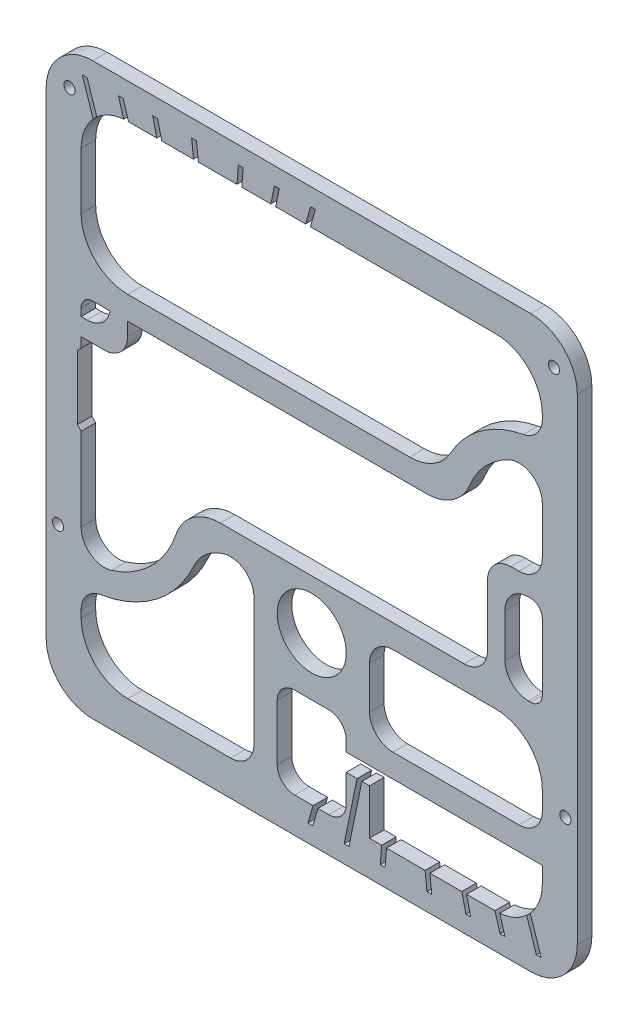
SolidWorks part; units mm, degrees
ref_plane "Front Plane" through (0, 0, 0) normal (0, 0, 1) x (1, 0, 0)
ref_plane "Top Plane" through (0, 0, 0) normal (0, 1, 0) x (1, 0, 0)
ref_plane "Right Plane" through (0, 0, 0) normal (1, 0, 0) x (0, 0, -1)
sketch "Sketch1" plane through (0, 0, 0) normal (0, 0, 1) x (1, 0, 0)
  line L0 (44.642, 23.7892) -> (44.642, 19.9792) construction
  line L1 (-8.1388, 23.7892) -> (49.7286, 23.7892)
  line L2 (-8.1388, 23.7892) -> (-8.1388, -38.311)
  line L3 (-8.1388, -38.311) -> (49.7286, -38.311)
  line L4 (49.7286, 23.7892) -> (49.7286, -38.311)
  line L5 (45.9186, -34.501) -> (-4.3288, -34.501)
  line L6 (45.9186, -34.501) -> (45.9186, 19.9792)
  line L7 (45.9186, 19.9792) -> (-4.3288, 19.9792)
  line L8 (-4.3288, -34.501) -> (-4.3288, 19.9792)
  line L9 (44.642, 21.8842) -> (-35.1587, 21.8842) construction
  line L10 (-4.3288, -31.0517) -> (-8.1388, -31.0517) construction
  line L11 (-6.2338, -31.0517) -> (-6.2338, 6.9585) construction
  line L12 (20.6696, 21.8842) -> (21.1982, 21.8842) construction
  line L13 (-6.2338, -12.887) -> (-6.2338, -25.1298) construction
  line L14 (3.0779, -34.501) -> (3.0779, -38.311) construction
  line L15 (3.0779, -36.406) -> (37.3423, -36.406) construction
  line L17 (49.7286, 15.2205) -> (45.9186, 15.2205) construction
  line L18 (47.8236, 15.2205) -> (47.8236, -0.9437) construction
  line L19 (47.8236, -1.6348) -> (47.8236, 10.608) construction
  line L20 (20.9203, -36.406) -> (20.3916, -36.406) construction
  dimension "D1" = 3.81
  dimension "D2" = 3.81
extrude "Boss-Extrude1" add sketch "Sketch1" along normal blind 1.5875
sketch "Sketch2" plane through (0, 0, 0) normal (0, 0, -1) x (-1, 0, 0)
  line L0 (-45.9186, -34.501) -> (-45.9186, 19.9792) construction
  line L1 (-34.8696, 3.653) -> (4.3288, 3.653)
  line L2 (-45.9186, 3.653) -> (-45.9186, 0.7339)
  line L3 (-37.4096, 1.113) -> (4.3288, 1.113)
  line L4 (4.3288, 3.653) -> (4.3288, 1.113)
  line L5 (4.3288, 19.9792) -> (4.3288, -34.501) construction
  line L6 (-33.4496, 1.113) -> (-36.4496, 1.113) construction
  line L7 (1.2504, -12.887) -> (-36.4496, -12.887) construction
  line L8 (-45.9186, -15.427) -> (-8.8785, -15.427)
  line L9 (-45.9186, -15.427) -> (-45.9186, -12.887)
  line L10 (-45.9186, -12.887) -> (-6.5805, -12.887)
  line L11 (1.357, -21.2563) -> (14.2432, -21.2563) construction
  line L12 (4.3288, -23.7963) -> (4.3288, -26.3363)
  line L13 (-45.9186, 12.162) -> (-45.9186, 9.622)
  arc A0 (-45.9186, 9.622) -> (-37.4096, 1.113) centre (-45.9186, 1.113) cw
  arc A1 (-45.9186, 12.162) -> (-34.8696, 3.653) centre (-45.9186, 0.7339) cw
  arc A2 (4.3288, -23.7963) -> (-6.5805, -12.887) centre (4.3288, -12.887) cw
  arc A3 (-8.8785, -15.427) -> (4.3288, -26.3363) centre (4.3288, -12.887) ccw
  circle A5 centre (1.357, -18.2591) radius 2.9972 construction
  line M5 (-45.9186, -34.501) -> (-45.9186, 19.9792)
  line M7 (4.3288, 19.9792) -> (4.3288, -34.501)
  dimension "D5" = 2.54
  dimension "D1" = 2.54
  dimension "D2" = 2.54
  dimension "D3" = 2.54
  dimension "D4" = 2.54
  dimension "D6" = 2.54
  dimension "D7" = 2.54
extrude "Boss-Extrude2" add sketch "Sketch2" against normal up to surface (1.5875 mm away) contours A1 A0 L3 L1 M5 M7 | L10 L8 M5 M7 region at (15.2704, 3.1385, 0) region at (-3.8086, -25.0663, 0) up to face at (20.7949, -7.2609, 1.5875)
sketch "Sketch3" plane through (0, 0, 0) normal (0, 0, -1) x (-1, 0, 0)
  line L0 (-45.9186, -1.1649) -> (-39.9496, -1.1649)
  line L1 (-45.9186, -12.887) -> (-45.9186, 9.622) construction
  line L2 (-39.9496, -4.387) -> (-39.9496, -11.387) construction
  line L3 (-39.9496, -1.1649) -> (-39.9496, -12.887)
  line L4 (-45.9186, -12.887) -> (-6.5805, -12.887) construction
  line L5 (-39.9496, -12.887) -> (-41.8546, -12.887)
  line L6 (-41.8546, -12.887) -> (-41.8546, -3.0699)
  line L7 (-41.8546, -3.0699) -> (-45.9186, -3.0699)
  line L8 (-45.9186, -3.0699) -> (-45.9186, -1.1649)
  line L9 (-42.9468, 0.7401) -> (-53.4831, 0.7401) construction
  line L10 (-0.7296, 1.113) -> (-0.7296, -2.887)
  line L11 (-37.4096, 1.113) -> (4.3288, 1.113) construction
  line L12 (-1.9996, -2.887) -> (1.2504, -2.887) construction
  line L13 (-0.7296, -2.887) -> (4.3288, -2.887)
  line L14 (4.3288, 1.113) -> (4.3288, -23.7963) construction
  line L15 (4.3288, -2.887) -> (4.3288, -0.982)
  line L16 (4.3288, -0.982) -> (1.1754, -0.982)
  line L17 (1.1754, -0.982) -> (1.1754, 1.113)
  line L18 (1.1754, 1.113) -> (-0.7296, 1.113)
  circle A0 centre (-42.9468, 3.7373) radius 2.9972 construction
  dimension "D1" = 1.905
  dimension "D2" = 1.905
  dimension "D3" = 1.905
  dimension "D4" = 1.905
  dimension "D5" = 1.27
  dimension "D6" = 1.905
extrude "Boss-Extrude3" add sketch "Sketch3" against normal up to surface (1.5875 mm away) up to face at (21.2778, -6.3699, 1.5875)
fillet "Fillet1" radius 5.08 4 edges at (49.7286, -38.311, 0.7937) (-8.1388, -38.311, 0.7937) (-8.1388, 23.7892, 0.7937) (49.7286, 23.7892, 0.7937)
fillet "Fillet2" radius 5.08 10 edges at (8.8785, -15.427, 0.7937) (45.9186, -15.427, 0.7937) (45.9186, -34.501, 0.7937) (-4.3288, -34.501, 0.7937) (34.8696, 3.653, 0.7937) (-4.3288, 3.653, 0.7937) (45.9186, 19.9792, 0.7937) (-4.3288, 19.9792, 0.7937) (6.5805, -12.887, 0.7937) (37.4096, 1.113, 0.7937)
fillet "Fillet3" radius 2.54 11 edges at (41.8546, -3.0699, 0.7938) (39.9496, -12.887, 0.7938) (41.8546, -12.887, 0.7938) (39.9496, -1.1649, 0.7938) (45.9186, -1.1649, 0.7938) (-1.1754, -0.982, 0.7938) (0.7296, -2.887, 0.7938) (45.9186, 9.622, 0.7937) (-4.3288, -26.3363, 0.7937) (-4.3288, -23.7963, 0.7937) (45.9186, 12.162, 0.7937)
fillet "Fillet4" radius 1.27 3 edges at (45.9186, -12.887, 0.7937) (45.9186, -3.0699, 0.7938) (-4.3288, 1.113, 0.7937)
sketch "Sketch5" plane through (0, 0, 0) normal (0, 0, -1) x (-1, 0, 0)
  line L0 (-40.8386, -15.427) -> (-12.5612, -15.427) construction
  line L1 (-27.0941, -15.427) -> (-14.4957, -15.427)
  line L2 (-27.0941, -15.427) -> (-27.0941, -34.501)
  line L3 (-27.0941, -34.501) -> (-14.4957, -34.501)
  line L4 (-14.4957, -15.427) -> (-14.4957, -34.501)
  line L5 (-0.7512, -34.501) -> (-40.8386, -34.501) construction
  line L6 (-24.5541, -18.2972) -> (-27.0941, -18.2972) construction
  line L9 (-17.0357, -18.2972) -> (-14.4957, -18.2972) construction
  circle A1 centre (-20.7949, -18.2972) radius 3.7592 construction
  dimension "D1" = 2.54
extrude "Boss-Extrude4" add sketch "Sketch5" against normal up to surface (1.5875 mm away) up to face at (-3.29, -0.0173, 1.5875)
sketch "Sketch6" plane through (0, 0, 0) normal (0, 0, -1) x (-1, 0, 0)
  circle A0 centre (-20.7949, -18.2972) radius 3.7592 construction
  circle A1 centre (-20.7949, -18.2972) radius 3.7592
extrude "Cut-Extrude2" cut sketch "Sketch6" against normal up to surface (1.5875 mm away) up to face at (4.8008, -25.4732, 1.5875)
sketch "Sketch7" plane through (0, 0, 0) normal (0, 0, -1) x (-1, 0, 0)
  line L0 (-27.0941, -15.427) -> (-27.0941, -34.501) construction
  line L1 (-24.5541, -24.5964) -> (-17.0357, -24.5964)
  line L2 (-24.5541, -24.5964) -> (-24.5541, -34.501)
  line L3 (-24.5541, -34.501) -> (-17.0357, -34.501)
  line L4 (-17.0357, -24.5964) -> (-17.0357, -34.501)
  line L5 (-14.4957, -34.501) -> (-14.4957, -15.427) construction
  line L6 (-0.7512, -34.501) -> (-14.4957, -34.501) construction
  line L7 (-20.7949, -22.0564) -> (-6.5424, -22.0564) construction
  line L8 (-20.7949, -22.0564) -> (-20.7949, -21.3452) construction
  circle A0 centre (-20.7949, -18.2972) radius 3.7592 construction
  dimension "D1" = 2.54
  dimension "D2" = 2.54
  dimension "D3" = 2.54
extrude "Cut-Extrude3" cut sketch "Sketch7" against normal up to surface (1.5875 mm away) up to face at (24.5541, -18.2972, 1.5875)
fillet "Fillet5" radius 1.905 4 edges at (24.5541, -34.501, 0.7937) (17.0357, -34.501, 0.7938) (17.0357, -24.5964, 0.7938) (24.5541, -24.5964, 0.7938)
sketch "Sketch8" plane through (0, 0, 0) normal (0, 0, -1) x (-1, 0, 0)
  line L0 (-45.9186, -29.421) -> (-45.9186, -20.507) construction
  line L1 (-45.9186, -25.103) -> (-27.0941, -25.103)
  line L2 (-45.9186, -25.103) -> (-45.9186, -27.643)
  line L3 (-45.9186, -27.643) -> (-27.0941, -27.643)
  line L4 (-27.0941, -25.103) -> (-27.0941, -27.643)
  line L5 (-27.0941, -15.427) -> (-27.0941, -34.501) construction
  line L6 (-45.7916, -27.643) -> (-20.3916, -27.643) construction
  dimension "D1" = 2.54
extrude "Boss-Extrude5" add sketch "Sketch8" against normal up to surface (1.5875 mm away) up to face at (20.7949, -29.5487, 1.5875)
fillet "Fillet6" radius 2.54 5 edges at (27.0941, -15.427, 0.7937) (14.4957, -15.427, 0.7937) (14.4957, -34.501, 0.7937) (27.0941, -25.103, 0.7937) (45.9186, -25.103, 0.7937)
sketch "Sketch4" plane through (0, 0, 0) normal (0, 0, -1) x (-1, 0, 0)
  line L0 (3.2504, -2.887) -> (4.7504, -4.387) construction
  line L1 (4.7504, -11.387) -> (3.2504, -12.887) construction
  line L2 (3.2504, -2.887) -> (4.7504, -4.387)
  line L3 (4.7504, -11.387) -> (3.2504, -12.887)
  line L4 (4.7504, -4.387) -> (4.7504, -11.387) construction
  line L5 (4.7504, -4.387) -> (4.7504, -11.387)
  line L6 (3.2504, -2.887) -> (3.2504, -12.887)
  line L32 (4.2018, 13.1212) -> (4.2018, 15.0262)
  line L33 (4.2018, 15.0262) -> (1.9364, 15.0262)
  line L34 (1.9364, 15.0262) -> (4.2018, 21.8842)
  line L35 (4.2018, 21.8842) -> (3.6731, 21.8842)
  line L36 (3.6731, 21.8842) -> (1.4078, 15.0262)
  line L37 (1.4078, 15.0262) -> (-1.7768, 15.0262)
  line L38 (-1.7768, 15.0262) -> (0.2648, 21.8842)
  line L39 (0.2648, 21.8842) -> (-0.2639, 21.8842)
  line L40 (-0.2639, 21.8842) -> (-2.3054, 15.0262)
  line L41 (-2.3054, 15.0262) -> (-5.0788, 15.0262)
  line L42 (-5.0788, 15.0262) -> (-3.469, 21.8842)
  line L43 (-3.469, 21.8842) -> (-3.9977, 21.8842)
  line L44 (-3.9977, 21.8842) -> (-5.6074, 15.0262)
  line L45 (-5.6074, 15.0262) -> (-8.4316, 15.0262)
  line L46 (-8.4316, 15.0262) -> (-7.7108, 21.8842)
  line L47 (-7.7108, 21.8842) -> (-8.2395, 21.8842)
  line L48 (-8.2395, 21.8842) -> (-8.9602, 15.0262)
  line L49 (-8.9602, 15.0262) -> (-12.267, 15.0262)
  line L50 (-12.267, 15.0262) -> (-12.7956, 21.8842)
  line L51 (-12.7956, 21.8842) -> (-13.3242, 21.8842)
  line L52 (-13.3242, 21.8842) -> (-12.7956, 15.0262)
  line L53 (-12.7956, 15.0262) -> (-15.3277, 15.0262)
  line L54 (-15.3277, 15.0262) -> (-16.7326, 21.8842)
  line L55 (-16.7326, 21.8842) -> (-17.2612, 21.8842)
  line L56 (-17.2612, 21.8842) -> (-15.8563, 15.0262)
  line L57 (-15.8563, 15.0262) -> (-18.6963, 15.0262)
  line L58 (-18.6963, 15.0262) -> (-20.6696, 21.8842)
  line L59 (-20.6696, 21.8842) -> (-21.1982, 21.8842)
  line L60 (-21.1982, 21.8842) -> (-19.225, 15.0262)
  line L61 (-19.225, 15.0262) -> (-21.1982, 15.0262)
  line L62 (-21.1982, 15.0262) -> (-21.1982, 13.1212)
  line L63 (-21.1982, 13.1212) -> (4.2018, 13.1212)
  line L64 (4.2018, 13.1212) -> (4.2018, 15.0262)
  line L65 (4.2018, 15.0262) -> (1.9364, 15.0262)
  line L66 (1.9364, 15.0262) -> (4.2018, 21.8842)
  line L67 (4.2018, 21.8842) -> (3.6731, 21.8842)
  line L68 (3.6731, 21.8842) -> (1.4078, 15.0262)
  line L69 (1.4078, 15.0262) -> (-1.7768, 15.0262)
  line L70 (-1.7768, 15.0262) -> (0.2648, 21.8842)
  line L71 (0.2648, 21.8842) -> (-0.2639, 21.8842)
  line L72 (-0.2639, 21.8842) -> (-2.3054, 15.0262)
  line L73 (-2.3054, 15.0262) -> (-5.0788, 15.0262)
  line L74 (-5.0788, 15.0262) -> (-3.469, 21.8842)
  line L75 (-3.469, 21.8842) -> (-3.9977, 21.8842)
  line L76 (-3.9977, 21.8842) -> (-5.6074, 15.0262)
  line L77 (-5.6074, 15.0262) -> (-8.4316, 15.0262)
  line L78 (-8.4316, 15.0262) -> (-7.7108, 21.8842)
  line L79 (-7.7108, 21.8842) -> (-8.2395, 21.8842)
  line L80 (-8.2395, 21.8842) -> (-8.9602, 15.0262)
  line L81 (-8.9602, 15.0262) -> (-12.267, 15.0262)
  line L82 (-12.267, 15.0262) -> (-12.7956, 21.8842)
  line L83 (-12.7956, 21.8842) -> (-13.3242, 21.8842)
  line L84 (-13.3242, 21.8842) -> (-12.7956, 15.0262)
  line L85 (-12.7956, 15.0262) -> (-15.3277, 15.0262)
  line L86 (-15.3277, 15.0262) -> (-16.7326, 21.8842)
  line L87 (-16.7326, 21.8842) -> (-17.2612, 21.8842)
  line L88 (-17.2612, 21.8842) -> (-15.8563, 15.0262)
  line L89 (-15.8563, 15.0262) -> (-18.6963, 15.0262)
  line L90 (-18.6963, 15.0262) -> (-20.6696, 21.8842)
  line L91 (-20.6696, 21.8842) -> (-21.1982, 21.8842)
  line L92 (-21.1982, 21.8842) -> (-19.225, 15.0262)
  line L93 (-19.225, 15.0262) -> (-21.1982, 15.0262)
  line L94 (-21.1982, 15.0262) -> (-21.1982, 13.1212)
  line L95 (-21.1982, 13.1212) -> (4.2018, 13.1212)
  line L96 (-45.7916, -27.643) -> (-45.7916, -29.548)
  line L97 (-45.7916, -29.548) -> (-43.5263, -29.548)
  line L98 (-43.5263, -29.548) -> (-45.7916, -36.406)
  line L99 (-45.7916, -36.406) -> (-45.263, -36.406)
  line L100 (-45.263, -36.406) -> (-42.9976, -29.548)
  line L101 (-42.9976, -29.548) -> (-39.8131, -29.548)
  line L102 (-39.8131, -29.548) -> (-41.8546, -36.406)
  line L103 (-41.8546, -36.406) -> (-41.326, -36.406)
  line L104 (-41.326, -36.406) -> (-39.2845, -29.548)
  line L105 (-39.2845, -29.548) -> (-36.5111, -29.548)
  line L106 (-36.5111, -29.548) -> (-38.1208, -36.406)
  line L107 (-38.1208, -36.406) -> (-37.5922, -36.406)
  line L108 (-37.5922, -36.406) -> (-35.9825, -29.548)
  line L109 (-35.9825, -29.548) -> (-33.1583, -29.548)
  line L110 (-33.1583, -29.548) -> (-33.879, -36.406)
  line L111 (-33.879, -36.406) -> (-33.3504, -36.406)
  line L112 (-33.3504, -36.406) -> (-32.6297, -29.548)
  line L113 (-32.6297, -29.548) -> (-29.3229, -29.548)
  line L114 (-29.3229, -29.548) -> (-28.7943, -36.406)
  line L115 (-28.7943, -36.406) -> (-28.2656, -36.406)
  line L116 (-28.2656, -36.406) -> (-28.7943, -29.548)
  line L117 (-28.7943, -29.548) -> (-26.2622, -29.548)
  line L118 (-26.2622, -29.548) -> (-24.8573, -36.406)
  line L119 (-24.8573, -36.406) -> (-24.3286, -36.406)
  line L120 (-24.3286, -36.406) -> (-25.7336, -29.548)
  line L121 (-25.7336, -29.548) -> (-22.8935, -29.548)
  line L122 (-22.8935, -29.548) -> (-20.9203, -36.406)
  line L123 (-20.9203, -36.406) -> (-20.3916, -36.406)
  line L124 (-20.3916, -36.406) -> (-22.3649, -29.548)
  line L125 (-22.3649, -29.548) -> (-20.3916, -29.548)
  line L126 (-20.3916, -29.548) -> (-20.3916, -27.643)
  line L127 (-20.3916, -27.643) -> (-45.7916, -27.643)
  line L128 (-45.7916, -27.643) -> (-45.7916, -29.548)
  line L129 (-45.7916, -29.548) -> (-43.5263, -29.548)
  line L130 (-43.5263, -29.548) -> (-45.7916, -36.406)
  line L131 (-45.7916, -36.406) -> (-45.263, -36.406)
  line L132 (-45.263, -36.406) -> (-42.9976, -29.548)
  line L133 (-42.9976, -29.548) -> (-39.8131, -29.548)
  line L134 (-39.8131, -29.548) -> (-41.8546, -36.406)
  line L135 (-41.8546, -36.406) -> (-41.326, -36.406)
  line L136 (-41.326, -36.406) -> (-39.2845, -29.548)
  line L137 (-39.2845, -29.548) -> (-36.5111, -29.548)
  line L138 (-36.5111, -29.548) -> (-38.1208, -36.406)
  line L139 (-38.1208, -36.406) -> (-37.5922, -36.406)
  line L140 (-37.5922, -36.406) -> (-35.9825, -29.548)
  line L141 (-35.9825, -29.548) -> (-33.1583, -29.548)
  line L142 (-33.1583, -29.548) -> (-33.879, -36.406)
  line L143 (-33.879, -36.406) -> (-33.3504, -36.406)
  line L144 (-33.3504, -36.406) -> (-32.6297, -29.548)
  line L145 (-32.6297, -29.548) -> (-29.3229, -29.548)
  line L146 (-29.3229, -29.548) -> (-28.7943, -36.406)
  line L147 (-28.7943, -36.406) -> (-28.2656, -36.406)
  line L148 (-28.2656, -36.406) -> (-28.7943, -29.548)
  line L149 (-28.7943, -29.548) -> (-26.2622, -29.548)
  line L150 (-26.2622, -29.548) -> (-24.8573, -36.406)
  line L151 (-24.8573, -36.406) -> (-24.3286, -36.406)
  line L152 (-24.3286, -36.406) -> (-25.7336, -29.548)
  line L153 (-25.7336, -29.548) -> (-22.8935, -29.548)
  line L154 (-22.8935, -29.548) -> (-20.9203, -36.406)
  line L155 (-20.9203, -36.406) -> (-20.3916, -36.406)
  line L156 (-20.3916, -36.406) -> (-22.3649, -29.548)
  line L157 (-22.3649, -29.548) -> (-20.3916, -29.548)
  line L158 (-20.3916, -29.548) -> (-20.3916, -27.643)
  line L159 (-20.3916, -27.643) -> (-45.7916, -27.643)
  dimension "D1" = 0
  dimension "D2" = 0
extrude "Cut-Extrude1" cut sketch "Sketch4" against normal up to surface (1.5875 mm away) up to face at (37.5833, -30.9522, 1.5875)
sketch "Sketch9" plane through (0, 0, 0) normal (0, 0, -1) x (-1, 0, 0)
  circle A0 centre (-47.1886, 19.9792) radius 0.6096 construction
  circle A1 centre (5.5988, 19.9792) radius 0.6096 construction
  circle A2 centre (6.8434, -21.8532) radius 0.6096 construction
  circle A3 centre (-48.4332, -21.8532) radius 0.6096 construction
  circle A4 centre (-47.1886, 19.9792) radius 0.6096
  circle A5 centre (5.5988, 19.9792) radius 0.6096
  circle A6 centre (6.8434, -21.8532) radius 0.6096
  circle A7 centre (-48.4332, -21.8532) radius 0.6096
extrude "Cut-Extrude4" cut sketch "Sketch9" against normal up to surface (1.5875 mm away) up to face at (18.1234, -5.3808, 1.5875)
